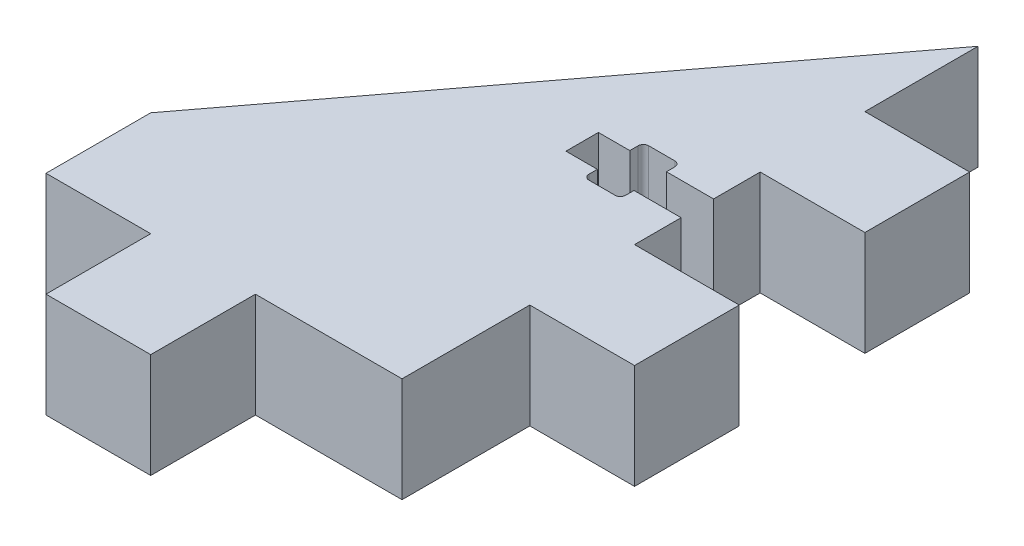
SolidWorks part; units mm, degrees
ref_plane "Front Plane" through (0, 0, 0) normal (0, 0, 1) x (1, 0, 0)
ref_plane "Top Plane" through (0, 0, 0) normal (0, 1, 0) x (1, 0, 0)
ref_plane "Right Plane" through (0, 0, 0) normal (1, 0, 0) x (0, 0, -1)
sketch "Sketch1" plane through (0, 0, 0) normal (0, 1, 0) x (1, 0, 0)
  line L0 (0, 0) -> (-14, 0)
  line L1 (-14, 0) -> (-14, -10)
  line L2 (-14, -10) -> (-24, -10)
  line L3 (-24, -10) -> (-24, 0)
  line L4 (-24, 0) -> (-34, 0)
  line L5 (-34, 0) -> (-34, 10)
  line L6 (-34, 10) -> (0, 55)
  line L7 (0, 55) -> (0, 44.2)
  line L8 (0, 44.2) -> (10, 44.2)
  line L9 (10, 44.2) -> (10, 34.2)
  line L10 (10, 34.2) -> (0, 34.2)
  line L11 (0, 34.2) -> (0, 22.2)
  line L12 (-24, 0) -> (-14, 0) construction
  line L13 (-19, 0) -> (-19, -10) construction
  line L14 (0, 17.2) -> (0, 12.2) construction
  line L15 (5, 12.2) -> (5, 21.2) construction
  line L16 (10, 34.2) -> (10, 22.2) construction
  line L17 (0, 28.2) -> (10, 28.2) construction
  line L24 (0, 22.2) -> (10, 22.2)
  line L25 (10, 22.2) -> (10, 12.2)
  line L26 (10, 12.2) -> (0, 12.2)
  line L27 (0, 12.2) -> (0, 0)
  line L32 (10, 39.2) -> (0, 39.2) construction
  line L33 (0, 39.2) -> (0, 34.2) construction
  line L34 (10, 17.2) -> (0, 17.2) construction
  line L35 (0, 17.2) -> (0, 22.2) construction
  dimension "D1" = 10
  dimension "D2" = 10
  dimension "D3" = 10
  dimension "D7" = 10
  dimension "D8" = 10
  dimension "D10" = 10
  dimension "D11" = 10
  dimension "D12" = 10
  dimension "D9" = 55
  dimension "D4" = 22
  dimension "D6" = 24
  dimension "D5" = 28.2
extrude "Boss-Extrude1" add sketch "Sketch1" along normal blind 10
sketch "Sketch2" [suppressed] plane through (0, 8, 0) normal (0, 1, 0) x (1, 0, 0)
  line L0 (0, 29.9) -> (0, 25.9) construction
  line L1 (0, 27.9) -> (-7.2, 27.9) construction
  line L2 (-7.2, 25.9) -> (-7.2, 29.9) construction
  line L3 (7.5, 36.4) -> (7.5, 20.4) construction
  line L4 (0, 36.4) -> (7.5, 36.4) construction
  line L5 (0, 27.9) -> (7.5, 27.9) construction
sketch "Sketch3" plane through (0, 10, 0) normal (0, 1, 0) x (1, 0, 0)
  line L0 (0, 28.2) -> (-11, 28.2) construction
  line L1 (0, 22.2) -> (0, 34.2) construction
  line L2 (-11, 29.75) -> (-8, 29.75)
  line L3 (-8, 29.75) -> (-8, 30.55)
  line L4 (-7.5, 31.05) -> (-5, 31.05)
  line L5 (-4.5, 30.55) -> (-4.5, 29.75)
  line L6 (-4.5, 29.75) -> (0, 29.75)
  line L7 (0, 29.75) -> (0, 26.65)
  line L8 (-11, 29.75) -> (-11, 26.65)
  line L9 (-4.5, 26.65) -> (0, 26.65)
  line L10 (-4.5, 25.85) -> (-4.5, 26.65)
  line L11 (-7.5, 25.35) -> (-5, 25.35)
  line L12 (-8, 26.65) -> (-8, 25.85)
  line L13 (-11, 26.65) -> (-8, 26.65)
  arc A0 (-8, 30.55) -> (-7.5, 31.05) centre (-7.5, 30.55) cw
  arc A1 (-5, 31.05) -> (-4.5, 30.55) centre (-5, 30.55) cw
  arc A2 (-5, 25.35) -> (-4.5, 25.85) centre (-5, 25.85) ccw
  arc A3 (-8, 25.85) -> (-7.5, 25.35) centre (-7.5, 25.85) ccw
  point P12 (-8, 31.05)
  point P15 (-4.5, 31.05)
  point P26 (-4.5, 25.35)
  point P27 (-8, 25.35)
  dimension "D7" = 0.5
  dimension "D1" = 11
  dimension "D3" = 1.55
  dimension "D2" = 8
  dimension "D4" = 3.5
  dimension "D5" = 2.85
  dimension "D6" = 1.55
extrude "Cut-Extrude1" cut sketch "Sketch3" against normal through all
equation "\"Y-ROD-SPACING\"=75"
equation "\"Y-BED-OFFSET\"=2"
equation "\"Y-BED-ROD-INSET\"=3.5"
equation "\"T-SLOT-NUT-FILLET-RADIUS\"=0.5"
equation "\"T-SLOT-SCREW-SHAFT-RADIUS\"=1.55"
equation "\"T-SLOT-SCREW-SHAFT-CUTOUT-LENGTH\"=11.0"
equation "\"T-SLOT-NUT-DEPTH\"=3.5"
equation "\"T-SLOT-NUT-WIDTH\"=2.85"
equation "\"T-SLOT-NUT-END-DISTANCE\"=8"
equation "\"ACRYLIC-TAB-CUTOUT-SIZE\"=\"ACRYLIC-THICKNESS\"+\"ACRYLIC-TAB-TOLERANCE\"*2"
equation "\"ACRYLIC-TAB-WIDTH\"=\"ACRYLIC-THICKNESS\""
equation "\"ACRYLIC-M3-HOLE\"=2.9"
equation "\"SMOOTHROD-CAP-SCREW-DISTANCE\"=20"
equation "\"FRAME-WIDTH-INNER\"=370"
equation "\"NEMA17-HOLE-SPACING\"=31"
equation "\"NEMA17-CENTRAL-CUTOUT\"=22.5"
equation "\"D3@Sketch1\"=\"ACRYLIC-TAB-WIDTH\""
equation "\"D12@Sketch1\"=\"ACRYLIC-TAB-WIDTH\""
equation "\"D2@Sketch1\"=\"ACRYLIC-TAB-WIDTH\""
equation "\"D11@Sketch1\"=\"ACRYLIC-TAB-WIDTH\""
equation "\"D1@Sketch1\"=\"ACRYLIC-TAB-WIDTH\""
equation "\"D10@Sketch1\"=\"ACRYLIC-TAB-WIDTH\""
equation "\"Z-BRACKET-REACH\"=55"
equation "\"D9@Sketch1\"=\"Z-BRACKET-REACH\""
equation "\"D6@Sketch3\"=\"T-SLOT-SCREW-SHAFT-RADIUS\""
equation "\"D3@Sketch3\"=\"T-SLOT-SCREW-SHAFT-RADIUS\""
equation "\"D4@Sketch3\"=\"T-SLOT-NUT-DEPTH\""
equation "\"D7@Sketch3\"=\"T-SLOT-NUT-FILLET-RADIUS\""
equation "\"D1@Sketch3\"=\"T-SLOT-SCREW-SHAFT-CUTOUT-LENGTH\""
equation "\"D5@Sketch3\"=\"T-SLOT-NUT-WIDTH\""
equation "\"D2@Sketch3\"=\"T-SLOT-NUT-END-DISTANCE\""
equation "\"X-ROD-SPACING\"=45"
equation "\"Z-ROD-SPACING\"=17.5"
equation "\"ACRYLIC-THICKNESS\"=10"
equation "\"ACRYLIC-THICKNESS2\"=4.5"
equation "\"TOP-BRACKET-SPACING\"=40"
equation "\"SMOOTHROD-X-LENGTH\"=350"
equation "\"SMOOTHROD-Y-LENGTH\"=350"
equation "\"SMOOTHROD-Z-LENGTH\"=350"
equation "\"SMOOTHROD-TIGHTENING-HEADROOM\"=.25"
equation "\"LEADSCREW-Z-LENGTH\"=300"
equation "\"SCREW-LENGTH-FRAME\"=\"ACRYLIC-THICKNESS\" + 10"
equation "\"SCREW-HEAD-RADIUS\"=6"
equation "\"PRINTED-X-SMOOTHROD-DIAMETER\"=8.4"
equation "\"PRINTED-X-SMOOTHROD-CUTOUT\"=10"
equation "\"PRINTED-X-BASE-HEIGHT\"=10"
equation "\"PRINTED-LM8UU-CUTOUT-SIZE\"=15.5"
equation "\"PRINTED-LM8UU-CUTOUT-LENGTH\"=24.5"
equation "\"PRINTED-X-IDLER-HEIGHT\"=16"
equation "\"PSU-MOUNTING-WIDTH\"=95"
equation "\"PSU-MOUNTING-HEIGHT\"=177"
equation "\"D1@Boss-Extrude1\"=\"ACRYLIC-THICKNESS\""
